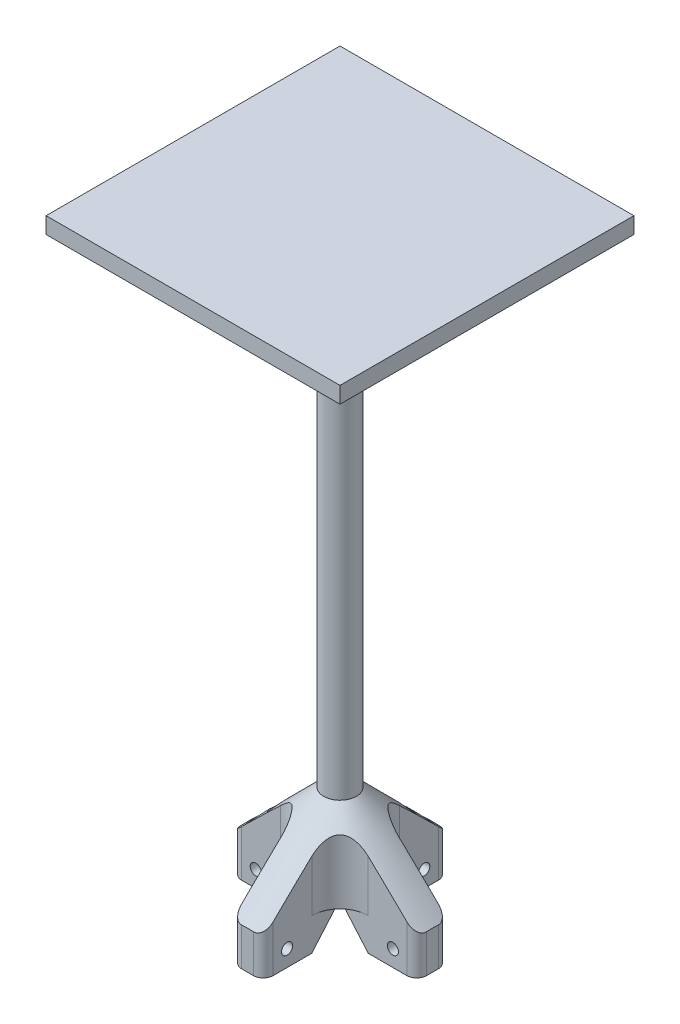
SolidWorks part; units mm, degrees
material "PLA"
ref_plane "Front Plane" through (0, 0, 0) normal (0, 0, 1) x (1, 0, 0)
ref_plane "Top Plane" through (0, 0, 0) normal (0, 1, 0) x (1, 0, 0)
ref_plane "Right Plane" through (0, 0, 0) normal (1, 0, 0) x (0, 0, -1)
sketch "Sketch8" plane through (0, 0, 0) normal (0, 1, 0) x (1, 0, 0)
  line L0 (13.7, 4.8) -> (28.3, 4.8)
  line L1 (-4.8, 13.7) -> (4.8, 13.7)
  line L2 (-4.8, 13.7) -> (-4.8, 28.3)
  line L3 (-4.8, 28.3) -> (4.8, 28.3)
  line L4 (4.8, 13.7) -> (4.8, 28.3)
  line L5 (-4.8, 13.7) -> (4.8, 28.3) construction
  line L6 (-4.8, 28.3) -> (4.8, 13.7) construction
  line L7 (13.7, 4.8) -> (13.7, -4.8)
  line L8 (13.7, -4.8) -> (28.3, -4.8)
  line L9 (28.3, 4.8) -> (28.3, -4.8)
  line L10 (4.8, -13.7) -> (4.8, -28.3)
  line L11 (4.8, -13.7) -> (-4.8, -13.7)
  line L12 (-4.8, -13.7) -> (-4.8, -28.3)
  line L13 (4.8, -28.3) -> (-4.8, -28.3)
  line L14 (-13.7, -4.8) -> (-28.3, -4.8)
  line L15 (-13.7, -4.8) -> (-13.7, 4.8)
  line L16 (-13.7, 4.8) -> (-28.3, 4.8)
  line L17 (-28.3, -4.8) -> (-28.3, 4.8)
  line L18 (-13.7, 4.8) -> (0, 4.8)
  line L19 (-13.7, -4.8) -> (0, -4.8)
  line L20 (4.8, 13.7) -> (4.8, 0)
  line L21 (-4.8, 13.7) -> (-4.8, 0)
  line L22 (13.7, -4.8) -> (0, -4.8)
  line L23 (13.7, 4.8) -> (0, 4.8)
  line L24 (-4.8, -13.7) -> (-4.8, 0)
  line L25 (4.8, -13.7) -> (4.8, 0)
  point P0 (0, 21)
  point P21 (0, 0)
  point P38 (0, 0)
  dimension "D1" = 21
  dimension "D2" = 9.6
  dimension "D3" = 4
  dimension "D5" = 14.6
  dimension "D4" = 4
extrude "Boss-Extrude4" add sketch "Sketch8" along normal blind 1.5 separate body contours L17 L14 L15 L16 | L1 L4 L3 L2 | L9 L0 L7 L8 | L13 L10 L11 L12 | L19 L24 L21 L18 L15 | L23 L20 L1 L21 L18 | L25 L22 L7 L23 L20 | L11 L25 L22 L19 L24 | L24 L19 | L18 L21 | L20 L23 | L22 L25 region at (21, 0, 0) region at (9.25, 0, 0) region at (0, 0, -9.25) region at (0, 0, 0) region at (0, 0, 9.25) region at (0, 0, -21) region at (0, 0, 21) region at (-9.25, 0, 0) region at (-21, 0, 0)
sketch "Sketch7" plane through (0, 1.5, 0) normal (0, 1, 0) x (1, 0, 0)
  circle A0 centre (0, 0) radius 5
  dimension "D1" = 10
extrude "Boss-Extrude3" add sketch "Sketch7" along normal blind 170
fillet "Fillet3" radius 8.65 4 edges at (4.8, 0.75, -4.8) (4.8, 0.75, 4.8) (-4.8, 0.75, 4.8) (-4.8, 0.75, -4.8)
sketch "Sketch13" plane through (0, 0, 0) normal (0, -1, 0) x (1, 0, 0)
  line L0 (-4.8, -28.3) -> (-4.8, -13.45) construction
  line L1 (-4.8, -28.3) -> (4.8, -28.3) construction
  line L2 (-4.8, -28.3) -> (-4.8, -13.45)
  line L3 (-4.8, -28.3) -> (4.8, -28.3)
  line L4 (4.8, -28.3) -> (4.8, -13.45) construction
  line L5 (-4.8, -28.3) -> (4.8, -28.3)
  line L6 (-4.8, -28.3) -> (-4.8, -13.45)
  line L7 (-4.8, -13.45) -> (4.8, -13.45)
  line L8 (4.8, -28.3) -> (4.8, -13.45)
  line L9 (-28.3, 4.8) -> (-13.45, 4.8)
  line L10 (-28.3, 4.8) -> (-28.3, -4.8)
  line L11 (-28.3, -4.8) -> (-13.45, -4.8)
  line L12 (-13.45, 4.8) -> (-13.45, -4.8)
  line L13 (4.8, 28.3) -> (4.8, 13.45)
  line L14 (4.8, 28.3) -> (-4.8, 28.3)
  line L15 (-4.8, 28.3) -> (-4.8, 13.45)
  line L16 (4.8, 13.45) -> (-4.8, 13.45)
  line L17 (28.3, -4.8) -> (13.45, -4.8)
  line L18 (28.3, -4.8) -> (28.3, 4.8)
  line L19 (28.3, 4.8) -> (13.45, 4.8)
  line L20 (13.45, -4.8) -> (13.45, 4.8)
  point P21 (0, 0)
  line M10 (-28.3, 4.8) -> (-28.3, -4.8)
  line M11 (-28.3, -4.8) -> (-13.45, -4.8)
  line M14 (-4.8, -28.3) -> (4.8, -28.3)
  line M15 (4.8, -28.3) -> (4.8, -13.45)
  line M17 (13.45, -4.8) -> (28.3, -4.8)
  line M18 (28.3, -4.8) -> (28.3, 4.8)
  line M19 (28.3, 4.8) -> (13.45, 4.8)
  line M21 (4.8, 13.45) -> (4.8, 28.3)
  line M22 (4.8, 28.3) -> (-4.8, 28.3)
  line M23 (-4.8, 28.3) -> (-4.8, 13.45)
  line M25 (-13.45, 4.8) -> (-28.3, 4.8)
  dimension "D1" = 14.85
  dimension "D2" = 4
extrude "Boss-Extrude7" add sketch "Sketch13" along normal blind 10 contours L7 L2 M14 M15 | L12 M25 M10 M11 | L16 M21 M22 M23 | L20 M17 M18 M19 region at (0, 0, -20.875) region at (-20.875, 0, 0) region at (0, 0, 20.875) region at (20.875, 0, 0)
hole_wizard "M3 Clearance Hole2" positions "Sketch9" profile "Sketch10" hole size "M3" standard "ANSI Metric" end condition up to next
sketch "Sketch9" plane through (-4.8, 2.575, 0) normal (1, 0, 0) x (0, -1, 0)
  line L2 (1.075, -4.8) -> (1.075, 4.8) construction
  line L3 (1.075, 5) -> (1.075, -5) construction
  line L4 (1.075, 5) -> (1.075, -5)
  line L7 (12.575, 13.45) -> (2.575, 13.45) construction
  line L8 (12.575, 13.45) -> (2.575, 13.45)
  point P15 (1.075, 0)
  point P38 (7.575, 21)
  point P45 (7.575, 13.45)
  dimension "D1" = 21
sketch "Sketch10" plane through (-4.8, -5, -21) normal (0, 1, 0) x (0, 0, 1)
  line L0 (0, 0) -> (0, 9.601)
  line L1 (0, 9.601) -> (1.7, 9.601)
  line L2 (1.7, 9.601) -> (1.7, 0)
  line L5 (1.7, 0) -> (0, 0)
  line L11 (0, -6.35) -> (0, 107.95) construction
  dimension "Thru Hole Dia." = 3.4
  dimension "Thru Hole Depth" = 9.601
pattern_circular "CirPattern1" count 4 over 360 about axis through (0, 171.5, 0) along (0, -1, 0) of "M3 Clearance Hole2" reverse direction yes
fillet "Fillet8" radius 3 8 edges at (4.8, -4.25, -28.3) (-4.8, -4.25, -28.3) (28.3, -4.25, -4.8) (28.3, -4.25, 4.8) (4.8, -4.25, 28.3) (-4.8, -4.25, 28.3) (-28.3, -4.25, 4.8) (-28.3, -4.25, -4.8)
sketch "Sketch11" plane through (0, 171.5, 0) normal (0, 1, 0) x (1, 0, 0)
  line L1 (-45, 45) -> (45, 45)
  line L2 (-45, 45) -> (-45, -45)
  line L3 (-45, -45) -> (45, -45)
  line L4 (45, 45) -> (45, -45)
  line L5 (-45, 45) -> (45, -45) construction
  line L6 (-45, -45) -> (45, 45) construction
  point P0 (0, 0)
  dimension "D1" = 90
extrude "Boss-Extrude5" add sketch "Sketch11" along normal blind 5
chamfer "Chamfer1" distance 23.5 angle 45 1 edges at (0, 1.5, 5)
fillet "Fillet5" radius 20 1 edges at (0, 171.5, 5)
chamfer "Chamfer2" distance 10 distance2 8.6 4 edges at (13.45, 0, 0) (0, 0, 13.45) (-13.45, 0, 0) (0, 0, -13.45) first distance on face at (13.45, -5, 0) first distance on face at (0, -5, 13.45) first distance on face at (-13.45, -5, 0) first distance on face at (0, -5, -13.45)
sketch "Sketch14" plane through (0, 0, 0) normal (0, -1, 0) x (1, 0, 0)
  circle A0 centre (0, 0) radius 5 construction
  circle A1 centre (0, 0) radius 5
  circle A2 centre (0, 0) radius 2.3
  dimension "D1" = 4.6
extrude "Cut-Extrude1" cut sketch "Sketch14" against normal offset from surface (174.5 mm away) 2 contours A2 region at (0, 0, 0) up to face at (0, 176.5, 0)
